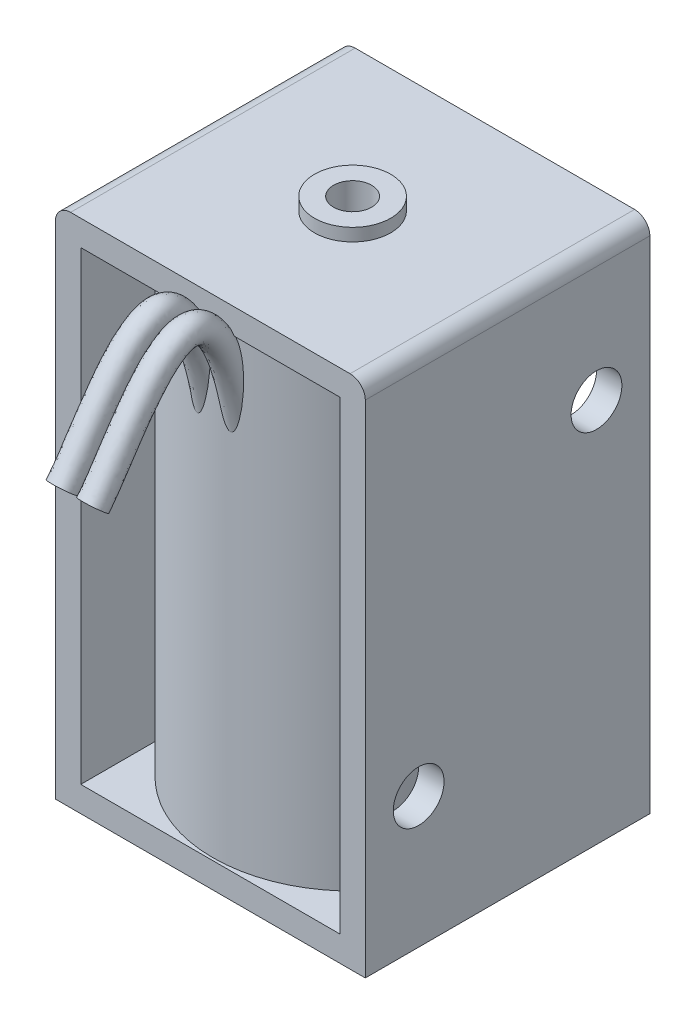
SolidWorks part; units mm, degrees
material "1023 炭素鋼板 (SS)"
ref_plane "Front" through (0, 0, 0) normal (0, 0, 1) x (1, 0, 0)
ref_plane "Top" through (0, 0, 0) normal (0, 1, 0) x (1, 0, 0)
ref_plane "Right" through (0, 0, 0) normal (1, 0, 0) x (0, 0, -1)
sketch "ｽｹｯﾁ1" plane through (0, 0, 0) normal (0, 1, 0) x (1, 0, 0)
  line L1 (0, 0) -> (12.2, 0)
  line L2 (0, 0) -> (0, 11.2)
  line L3 (0, 11.2) -> (12.2, 11.2)
  line L4 (12.2, 0) -> (12.2, 11.2)
  dimension "D1" = 12.2
  dimension "D2" = 11.2
extrude "ﾎﾞｽ - 押し出し1" add sketch "ｽｹｯﾁ1" along normal blind 20.3
sketch "ｽｹｯﾁ2" plane through (0, 0, 0) normal (0, 0, 1) x (1, 0, 0)
  line L0 (1, 1) -> (11.2, 1)
  line L1 (11.2, 1) -> (11.2, 19.3)
  line L2 (11.2, 19.3) -> (1, 19.3)
  line L3 (1, 19.3) -> (1, 1)
  line L4 (0, 0) -> (12.2, 0)
  line L5 (12.2, 0) -> (12.2, 20.3)
  line L6 (12.2, 20.3) -> (0, 20.3)
  line L7 (0, 20.3) -> (0, 0)
  line L8 (0, 0) -> (12.2, 0)
  line L9 (12.2, 0) -> (12.2, 20.3)
  line L10 (12.2, 20.3) -> (0, 20.3)
  line L11 (0, 20.3) -> (0, 0)
  dimension "D1" = 0
  dimension "D2" = 1
extrude "ｶｯﾄ - 押し出し1" cut sketch "ｽｹｯﾁ2" against normal through all contours L2 L3 L0 L1 region at (6.1, 10.15, 0)
sketch "ｽｹｯﾁ3" plane through (0, 20.3, 0) normal (0, 1, 0) x (1, 0, 0)
  line L0 (0, 11.2) -> (12.2, 0) construction
  line L1 (12.2, 0) -> (12.2, 11.2) construction
  line L2 (12.2, 11.2) -> (0, 0) construction
  circle A0 centre (6.1, 5.6) radius 1.5
  dimension "D1" = 3
extrude "ﾎﾞｽ - 押し出し2" add sketch "ｽｹｯﾁ3" along normal blind 0.5
sketch "ｽｹｯﾁ6" plane through (12.2, 0, 0) normal (1, 0, 0) x (0, 0, -1)
  line L0 (0, 0) -> (11.2, 0) construction
  line L1 (0, 20.3) -> (0, 0) construction
  circle A0 centre (9.1, 15.15) radius 1
  circle A1 centre (2.1, 5.15) radius 1
  dimension "D1" = 2
  dimension "D2" = 10
  dimension "D3" = 5.15
  dimension "D4" = 2.1
  dimension "D5" = 7
extrude "ｶｯﾄ - 押し出し2" cut sketch "ｽｹｯﾁ6" against normal blind 2
sketch "ｽｹｯﾁ7" plane through (0, 1, 0) normal (0, 1, 0) x (1, 0, 0)
  circle A0 centre (6.1, 5.6) radius 5.5
  dimension "D1" = 11
extrude "ﾎﾞｽ - 押し出し3" add sketch "ｽｹｯﾁ7" along normal up to surface (18.3 mm away) separate body up to face at (6.1, 19.3, -5.6)
sketch "ｽｹｯﾁ8" plane through (0, 0, 0) normal (0, -1, 0) x (1, 0, 0)
  circle A0 centre (6.1, -5.6) radius 2
  dimension "D1" = 4
extrude "ｶｯﾄ - 押し出し3" cut sketch "ｽｹｯﾁ8" against normal up to surface (19.3 mm away) up to face at (6.1, 19.3, -5.6)
sketch "ｽｹｯﾁ9" plane through (0, 20.8, 0) normal (0, 1, 0) x (1, 0, 0)
  circle A0 centre (6.1, 5.6) radius 0.75
  dimension "D1" = 1.5
extrude "ｶｯﾄ - 押し出し4" cut sketch "ｽｹｯﾁ9" against normal through all
ref_plane "平面1" through (5.5, 0, 0) normal (-1, 0, 0) x (0, 0, 1)
sketch "ｽｹｯﾁ10" plane through (5.5, 0, 0) normal (-1, 0, 0) x (0, 0, 1)
  spline S0 degree 3 poles (-0.8843, 14.3082) (0.5563, 24.944) (3.6114, 17.9644) (5.2292, 15.9755) knots 0 0 0 0 1 1 1 1
sweep "ｽｲｰﾌﾟ1" add path "ｽｹｯﾁ10" circular profile diameter 1 parameters "D3"=1
ref_plane "平面2" through (6.1, 0, 0) normal (1, 0, 0) x (0, 0, -1)
mirror "ﾐﾗｰ2" about plane through (6.1, 0, 0) normal (1, 0, 0) of "ｽｲｰﾌﾟ1"
fillet "ﾌｨﾚｯﾄ1" radius 0.6 2 edges at (0, 20.3, -5.6) (12.2, 20.3, -5.6)
